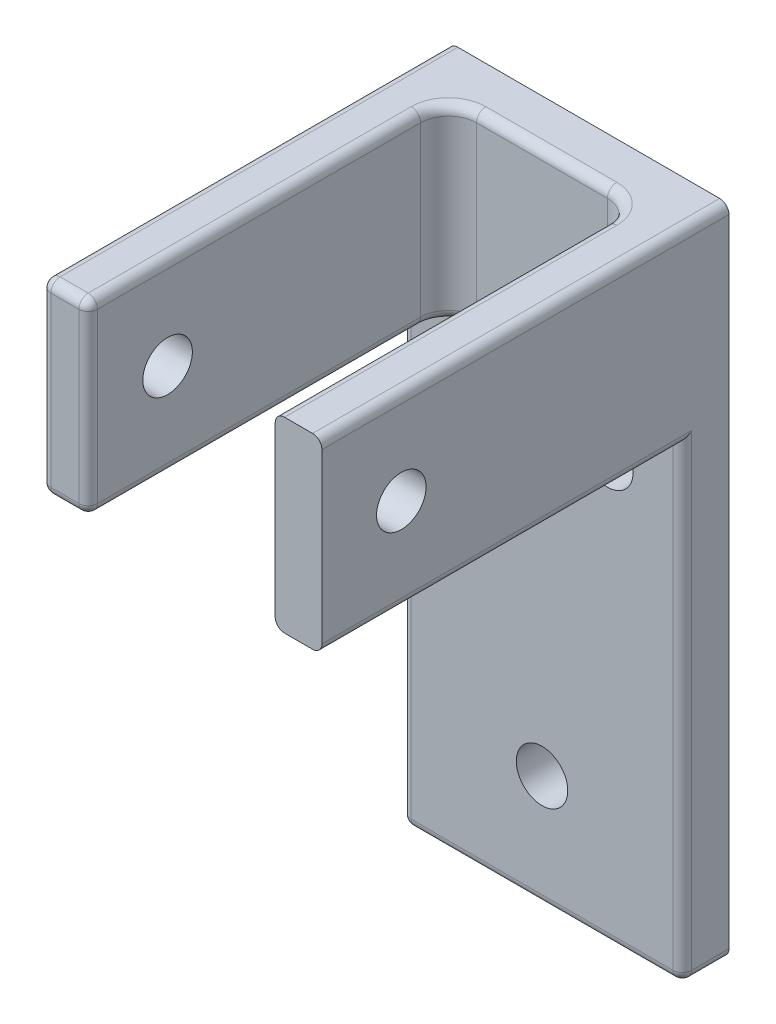
SolidWorks part; units mm, degrees
material "PETG"
ref_plane "Front Plane" through (0, 0, 0) normal (0, 0, 1) x (1, 0, 0)
ref_plane "Top Plane" through (0, 0, 0) normal (0, 1, 0) x (1, 0, 0)
ref_plane "Right Plane" through (0, 0, 0) normal (1, 0, 0) x (0, 0, -1)
sketch "Sketch1" plane through (0, 0, 0) normal (0, 0, 1) x (1, 0, 0)
  line L1 (15, -35) -> (-15, -35)
  line L2 (15, -35) -> (15, 35)
  line L3 (15, 35) -> (-15, 35)
  line L4 (-15, -35) -> (-15, 35)
  line L5 (15, -35) -> (-15, 35) construction
  line L6 (15, 35) -> (-15, -35) construction
  point P0 (0, 0)
  dimension "D1" = 30
  dimension "D2" = 70
extrude "Boss-Extrude1" add sketch "Sketch1" along normal blind 5
sketch "Sketch2" plane through (0, 0, 5) normal (0, 0, 1) x (1, 0, 0)
  line L0 (0, 35) -> (0, -35) construction
  line L1 (15, 35) -> (-15, 35) construction
  line L2 (-15, -35) -> (15, -35) construction
  line L3 (-15, 0) -> (15, 0) construction
  line L4 (-15, 35) -> (-15, -35) construction
  line L5 (15, -35) -> (15, 35) construction
  point P13 (-7, 10)
  point P15 (7, 10)
  point P17 (0, -23)
  dimension "D1" = 15
  dimension "D2" = 12
  dimension "D3" = 8
  dimension "D4" = 45
  dimension "D5" = 8
  dimension "D6" = 45
hole_wizard "M5 Clearance Hole1" positions "Sketch2" profile "Sketch3" hole size "M5" standard "ANSI Metric" end condition through all
sketch "Sketch3" plane through (0, -23, 5) normal (1, 0, 0) x (0, -1, 0)
  line L0 (0, 0) -> (0, 5)
  line L1 (0, 5) -> (2.75, 5)
  line L2 (2.75, 5) -> (2.75, 0)
  line L5 (2.75, 0) -> (0, 0)
  line L11 (0, -6.35) -> (0, 107.95) construction
  dimension "Thru Hole Dia." = 5.5
  dimension "Thru Hole Depth" = 5
sketch "Sketch4" plane through (0, 0, 5) normal (0, 0, 1) x (1, 0, 0)
  line L0 (15, 35) -> (-15, 35) construction
  line L1 (-15, 35) -> (-10, 35)
  line L2 (-15, 35) -> (-15, 15)
  line L3 (-15, 15) -> (-10, 15)
  line L4 (-10, 35) -> (-10, 15)
  line L6 (-15, 35) -> (-15, -35) construction
  line L8 (15, 35) -> (10, 35)
  line L9 (15, 35) -> (15, 15)
  line L10 (15, 15) -> (10, 15)
  line L11 (10, 35) -> (10, 15)
  dimension "D1" = 5
  dimension "D2" = 20
  dimension "D3" = 20
  dimension "D4" = 5
extrude "Boss-Extrude2" add sketch "Sketch4" along normal blind 38.542
hole_wizard "M5 Clearance Hole2" positions "Sketch8" profile "Sketch7" hole size "M5" standard "ANSI Metric" end condition through all
sketch "Sketch8" plane through (-15, 0, 0) normal (-1, 0, 0) x (0, 0, 1)
  line L6 (43.542, 25) -> (0, 25) construction
  line L7 (43.542, 35) -> (43.542, 15) construction
  line L8 (0, 35) -> (0, -35) construction
  line L9 (5, 15) -> (5, 35) construction
  line L10 (5, 15) -> (5, 35) construction
  line L11 (5, 35) -> (43.542, 35) construction
  point P0 (35.052, 25)
  dimension "D1" = 35.052
sketch "Sketch7" plane through (-15, 25, 35.052) normal (0, 1, 0) x (0, 0, 1)
  line L0 (0, 0) -> (0, 30)
  line L1 (0, 30) -> (2.65, 30)
  line L2 (2.65, 30) -> (2.65, 0)
  line L5 (2.65, 0) -> (0, 0)
  line L11 (0, -6.35) -> (0, 107.95) construction
  dimension "Thru Hole Dia." = 5.3
  dimension "Thru Hole Depth" = 30
fillet "Fillet1" radius 3 2 edges at (10, 25, 5) (-10, 25, 5)
fillet "Fillet2" radius 1 2 edges at (-10, 25, 43.542) (-15, 25, 43.542)
fillet "Fillet3" radius 1 17 edges at (9.1213, 15, 5.8787) (-9.1213, 15, 5.8787) (-10, 15, 25.271) (-10.2929, 15, 43.2491) (-12.5, 15, 43.542) (-14.7071, 15, 43.2491) (9.1213, 35, 5.8787) (0, 35, 5) (-9.1213, 35, 5.8787) (-10, 35, 25.271) (-10.2929, 35, 43.2491) (-12.5, 35, 43.542) (-14.7071, 35, 43.2491) (10, 35, 25.771) (10, 15, 25.771) (-15, 15, 23.771) (-15, 35, 21.271)
fillet "Fillet4" radius 1 2 edges at (15, 35, 21.771) (15, 15, 24.271)
fillet "Fillet5" radius 1 2 edges at (-15, -9.5, 5) (15, -9.5, 5)
fillet "Fillet6" radius 1 5 edges at (14.7071, -35, 4.7071) (0, -35, 5) (-14.7071, -35, 4.7071) (15, -35, 2) (-15, -35, 2)
